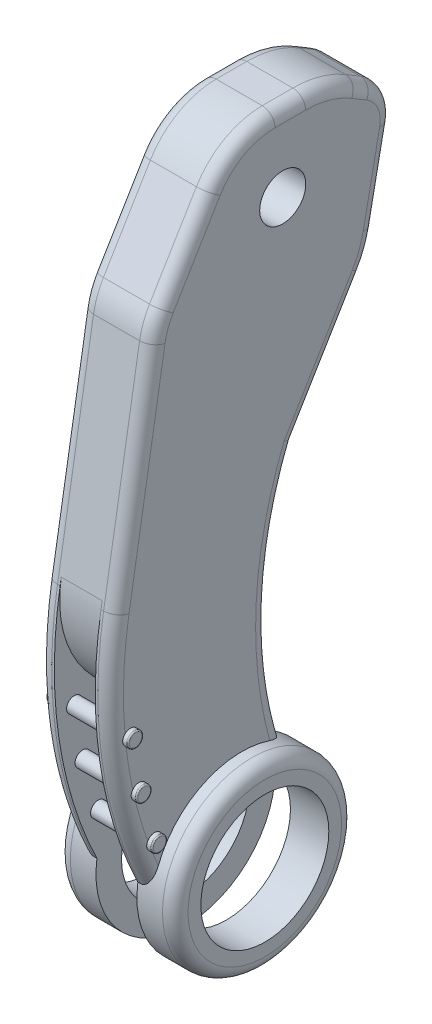
SolidWorks part; units mm, degrees
ref_plane "Front Plane" through (0, 0, 0) normal (0, 0, 1) x (1, 0, 0)
ref_plane "Top Plane" through (0, 0, 0) normal (0, 1, 0) x (1, 0, 0)
ref_plane "Right Plane" through (0, 0, 0) normal (1, 0, 0) x (0, 0, -1)
sketch "Sketch1" plane through (0, 0, 0) normal (1, 0, 0) x (0, 0, -1)
  line L0 (-25.4, 38.1) -> (25.4, 38.1)
  line L1 (25.4, 38.1) -> (57.15, 19.05)
  line L2 (57.15, 19.05) -> (44.45, -44.45)
  line L3 (-25.4, 38.1) -> (-63.5, -25.4)
  line L4 (-63.5, -25.4) -> (-82.55, -139.7)
  line L5 (6.35, -209.55) -> (25.4, -222.25)
  line L6 (-57.15, -279.4) -> (-38.1, -292.1)
  line L7 (44.45, -44.45) -> (6.35, -107.95)
  line L8 (-38.1, -292.1) -> (25.4, -222.25)
  circle A0 centre (0, 0) radius 11.43
  arc A1 (6.35, -209.55) -> (6.35, -107.95) centre (189.9518, -158.75) cw
  arc A2 (-82.55, -139.7) -> (-57.15, -279.4) centre (124.5152, -174.2109) ccw
  point P14 (0, 38.1)
  dimension "D1" = 22.86
  dimension "D17" = 190.5
  dimension "D2" = 38.1
  dimension "D3" = 50.8
  dimension "D4" = 31.75
  dimension "D5" = 19.05
  dimension "D6" = 63.5
  dimension "D7" = 12.7
  dimension "D8" = 38.1
  dimension "D9" = 63.5
  dimension "D10" = 114.3
  dimension "D11" = 19.05
  dimension "D12" = 63.5
  dimension "D13" = 38.1
  dimension "D14" = 139.7
  dimension "D15" = 25.4
  dimension "D16" = 101.6
  dimension "D18" = 19.05
  dimension "D19" = 12.7
extrude "Boss-Extrude1" add sketch "Sketch1" along normal mid plane 35.56
fillet "Fillet1" radius 38.1 2 edges at (0, 38.1, 25.4) (0, -25.4, 63.5)
fillet "Fillet2" radius 50.8 2 edges at (0, -44.45, -44.45) (0, 38.1, -25.4)
fillet "Fillet3" radius 20.32 1 edges at (0, 19.05, -57.15)
sketch "Sketch2" plane through (17.78, 0, 0) normal (1, 0, 0) x (0, 0, -1)
  line L0 (-38.1, -292.1) -> (25.4, -222.25) construction
  line L1 (6.35, -107.95) -> (25.4, -222.25)
  line L2 (25.4, -222.25) -> (4.8969, -244.8034)
  arc A0 (4.8969, -244.8034) -> (6.35, -107.95) centre (183.3985, -178.2642) cw
  dimension "D2" = 190.5
  dimension "D1" = 30.48
extrude "Cut-Extrude1" cut sketch "Sketch2" against normal up to next
fillet "Fillet4" radius 6.35 26 edges at (-17.78, -79.9727, -23.1364) (-17.78, -44.1772, -43.7444) (-17.78, -15.4067, -50.2587) (-17.78, 17.2138, -52.9992) (-17.78, 28.6391, -41.1682) (-17.78, 36.2567, -24.8894) (-17.78, 38.1, -3.7505) (-17.78, 33.1546, 22.6) (-17.78, 0.2027, 48.1384) (-17.78, -25.6352, 62.8612) (-17.78, -86.1178, 73.6196) (17.78, -79.9727, -23.1364) (17.78, -44.1772, -43.7444) (17.78, -15.4067, -50.2587) (17.78, 17.2138, -52.9992) (17.78, 28.6391, -41.1682) (17.78, 36.2567, -24.8894) (17.78, 38.1, -3.7505) (17.78, 33.1546, 22.6) (17.78, 0.2027, 48.1384) (17.78, -25.6352, 62.8612) (17.78, -86.1178, 73.6196) (-17.78, -176.2417, 7.0908) (17.78, -176.2417, 7.0908) (-17.78, -211.7628, 82.0202) (17.78, -211.7628, 82.0202)
sketch "Sketch3" plane through (0, 0, 0) normal (1, 0, 0) x (0, 0, -1)
  line L0 (-38.1, -292.1) -> (0.1113, -250.0676) construction
  circle A0 centre (-20.3108, -272.5319) radius 37.474
extrude "Boss-Extrude2" add sketch "Sketch3" along normal mid plane 38.1
sketch "Sketch4" plane through (19.05, 0, 0) normal (1, 0, 0) x (0, 0, -1)
  circle A0 centre (-20.3108, -272.5319) radius 44.45
  arc A1 (-3.8984, -238.8431) -> (-57.2051, -265.9662) centre (-20.3108, -272.5319) ccw construction
  dimension "D1" = 88.9
extrude "Boss-Extrude3" add sketch "Sketch4" along normal mid plane 20.32
mirror "Mirror1" about plane through (0, 0, 0) normal (1, 0, 0) of "Boss-Extrude3"
fillet "Fillet5" radius 6.35 2 edges at (-29.21, -272.5319, -24.1392) (29.21, -272.5319, -24.1392)
sketch "Sketch5" plane through (29.21, 0, 0) normal (1, 0, 0) x (0, 0, -1)
  circle A0 centre (-20.3108, -272.5319) radius 31.75
  circle A1 centre (-20.3108, -272.5319) radius 38.1 construction
  dimension "D1" = 63.5
extrude "Cut-Extrude2" cut sketch "Sketch5" against normal through all
sketch "Sketch6" plane through (0, 0, 0) normal (1, 0, 0) x (0, 0, -1)
  line L0 (-51.3806, -265.9949) -> (-6.9359, -170.321)
  line L1 (-6.9359, -170.321) -> (42.365, -321.2538)
  line L2 (42.365, -321.2538) -> (-147.8946, -308.5846)
  line L3 (-147.8946, -308.5846) -> (-51.3806, -265.9949)
  line L4 (-61.7288, -256.3965) -> (-56.4327, -268.3982) construction
  circle A0 centre (-20.3108, -272.5319) radius 31.75 construction
  arc A1 (6.35, -107.95) -> (1.107, -233.5821) centre (183.3985, -178.2642) ccw construction
  arc A2 (-76.2864, -140.7439) -> (-61.7288, -256.3965) centre (124.5152, -174.2109) ccw construction
  circle A3 centre (-20.3108, -272.5319) radius 44.45 construction
extrude "Cut-Extrude3" cut sketch "Sketch6" against normal mid plane 20.32
sketch "Sketch7" plane through (0, 0, 0) normal (1, 0, 0) x (0, 0, -1)
  line L1 (-83.243, -204.2696) -> (43.757, -204.2696)
  line L2 (-83.243, -204.2696) -> (-83.243, -356.6696)
  line L3 (-83.243, -356.6696) -> (43.757, -356.6696)
  line L4 (43.757, -204.2696) -> (43.757, -356.6696)
  arc A0 (-82.55, -139.7) -> (-64.2775, -265.9949) centre (124.5152, -174.2109) ccw construction
  dimension "D1" = 127
  dimension "D2" = 152.4
extrude "Cut-Extrude4" cut sketch "Sketch7" against normal mid plane 20.32
fillet "Fillet7" radius 58.42 1 edges at (0, -204.2696, 83.243)
sketch "Sketch8" plane through (-10.16, 0, 0) normal (1, 0, 0) x (0, 0, -1)
  circle A0 centre (-63.6273, -245.0347) radius 3.81
  circle A1 centre (-71.3171, -219.6347) radius 3.81
  circle A2 centre (-75.5165, -194.2347) radius 3.81
  arc A3 (-51.9915, -270.4347) -> (-75.5165, -194.2347) centre (124.5152, -174.2109) cw construction
  circle A4 centre (-20.3108, -272.5319) radius 31.75 construction
  arc A5 (-82.55, -139.7) -> (-64.2775, -265.9949) centre (124.5152, -174.2109) ccw construction
  dimension "D1" = 8.89
  dimension "D3" = 7.62
  dimension "D2" = 76.2
  dimension "D4" = 25.4
  dimension "D5" = 25.4
extrude "Boss-Extrude4" add sketch "Sketch8" along normal blind 30.48 and the other way blind 10.16
fillet "Fillet8" radius 0.635 6 edges at (-20.32, -194.2347, 71.7065) (-20.32, -219.6347, 67.5071) (-20.32, -245.0347, 59.8173) (20.32, -245.0347, 59.8173) (20.32, -219.6347, 67.5071) (20.32, -194.2347, 71.7065)
fillet "Fillet9" radius 15.24 1 edges at (0, -204.2696, 22.7065)
